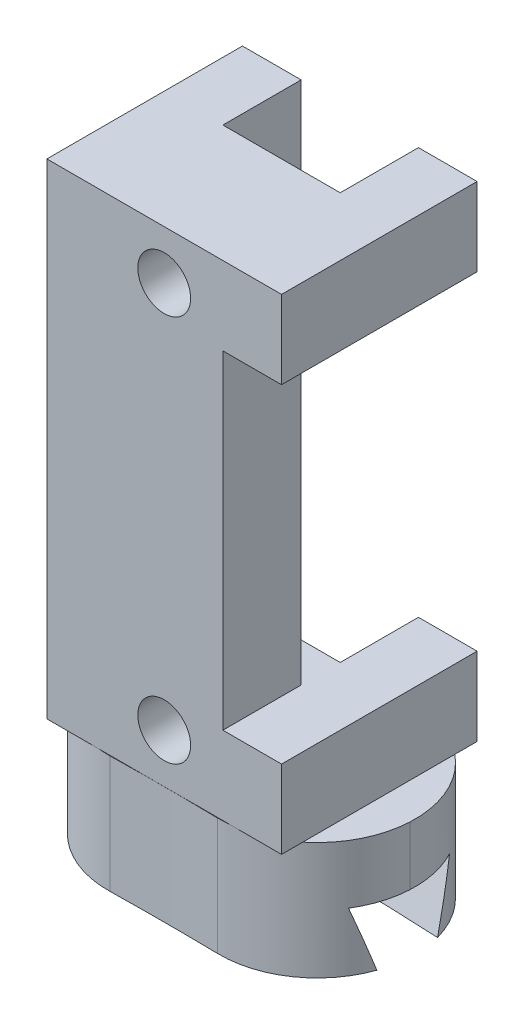
SolidWorks part; units mm, degrees
ref_plane "Front Plane" through (0, 0, 0) normal (0, 0, 1) x (1, 0, 0)
ref_plane "Top Plane" through (0, 0, 0) normal (0, 1, 0) x (1, 0, 0)
ref_plane "Right Plane" through (0, 0, 0) normal (1, 0, 0) x (0, 0, -1)
ref_axis "Axis2" through (0, 11, 0) along (0, -1, 0)
ref_plane "Plane2" through (0, 0, -150) normal (0, 0, 1) x (1, 0, 0)
sketch "Sketch7" plane through (0, 0, -150) normal (0, 0, 1) x (1, 0, 0)
  line L1 (-6, 24.8) -> (6, 24.8)
  line L2 (-6, 24.8) -> (-6, 0)
  line L4 (6, 24.8) -> (6, 0)
  line L7 (-6, 0) -> (6, 0)
  point P6 (6, 0)
  point P8 (0, 0)
  point P11 (0, 24.8)
  dimension "D1" = 24.8
  dimension "D2" = 12
extrude "Main" add sketch "Sketch7" along normal mid plane 10
sketch "Sketch8" plane through (0, 0, -145) normal (0, 0, 1) x (1, 0, 0)
  line L1 (-6, 24.8) -> (-6, 0) construction
  line L2 (6, 24.8) -> (-6, 24.8) construction
  circle A0 centre (0, 22.3) radius 1.35
  circle A1 centre (0, 2.5) radius 1.35
  dimension "D1" = 2.7
  dimension "D2" = 2.5
  dimension "D3" = 19.8
  dimension "D4" = 6
extrude "Holes" cut sketch "Sketch8" against normal through all
sketch "Sketch9" plane through (0, 0, -145) normal (0, 0, 1) x (1, 0, 0)
  line L1 (6, 24.8) -> (-6, 24.8)
  line L2 (6, 24.8) -> (6, 12.8)
  line L3 (6, 12.8) -> (-6, 12.8)
  line L4 (-6, 24.8) -> (-6, 12.8)
  dimension "D3" = 12
sketch "Sketch16" plane through (6, 0, 0) normal (1, 0, 0) x (0, 0, -1)
  line L1 (149, 20.8) -> (155, 20.8)
  line L2 (149, 20.8) -> (149, 4)
  line L3 (149, 4) -> (155, 4)
  line L4 (155, 20.8) -> (155, 4)
  line L5 (155, 0) -> (155, 24.8) construction
  dimension "D1" = 6
  dimension "D2" = 4
  dimension "D3" = 4
extrude "FixExtrusion" cut sketch "Sketch16" against normal through all
sketch "Sketch10" plane through (0, 0, 0) normal (1, 0, 0) x (0, 0, -1)
  line L0 (152.5, -3) -> (147.5, -3)
  line L1 (152.5, -3) -> (151.5, -6)
  line L3 (151.5, -6) -> (155, -6)
  line L4 (155, -6) -> (155, 0)
  line L5 (155, 0) -> (145, 0)
  line L6 (145, 0) -> (145, -6)
  line L7 (147.5, -3) -> (148.5, -6)
  line L9 (148.5, -6) -> (145, -6)
  line L10 (145, 0) -> (155, 0) construction
  point P9 (150, 0)
  point P12 (150, -3)
  dimension "D1" = 3
  dimension "D3" = 5
  dimension "D5" = 3
  dimension "D6" = 6
  dimension "D7" = 150
  dimension "D9" = 3.5
revolve "Support" add sketch "Sketch10" angle 6 mid plane about axis through (0, 11, 0) along (0, -1, 0) other way angle 6
fillet "Fillet1" radius 5 4 edges at (8.1121, -3, -154.7876) (-8.1121, -3, -154.7876) (7.5887, -3, -144.8013) (-7.5887, -3, -144.8013)
sketch "Sketch17" plane through (0, 0, -155) normal (0, 0, -1) x (-1, 0, 0)
  line L0 (-6, 24.8) -> (6, 24.8) construction
  line L1 (-3, 24.8) -> (3, 24.8)
  line L2 (-3, 24.8) -> (-3, 0)
  line L3 (-3, 0) -> (3, 0)
  line L4 (3, 24.8) -> (3, 0)
  line L5 (6, 0) -> (-6, 0) construction
  line L6 (-6, 20.8) -> (-6, 24.8) construction
  dimension "D1" = 6
  dimension "D2" = 3
extrude "Cut-Extrude1" cut sketch "Sketch17" against normal blind 4
sketch "Sketch18" plane through (0, 0, -149) normal (0, 0, -1) x (-1, 0, 0)
  line L0 (6, 4) -> (-6, 4) construction
  line L1 (-6, 20.8) -> (-3, 20.8)
  line L2 (-6, 20.8) -> (-6, 4)
  line L3 (-6, 4) -> (-3, 4)
  line L4 (-3, 20.8) -> (-3, 4)
  dimension "D1" = 3
extrude "Cut-Extrude2" cut sketch "Sketch18" against normal through all
